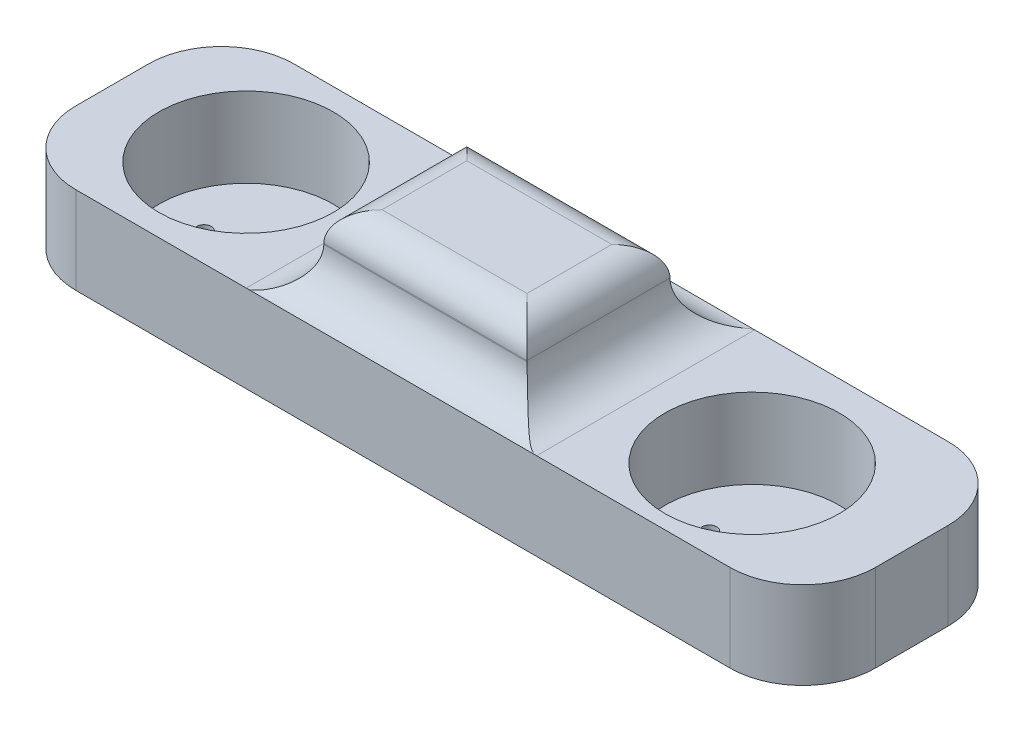
SolidWorks part; units mm, degrees
ref_plane "Front Plane" through (0, 0, 0) normal (0, 0, 1) x (1, 0, 0)
ref_plane "Top Plane" through (0, 0, 0) normal (0, 1, 0) x (1, 0, 0)
ref_plane "Right Plane" through (0, 0, 0) normal (1, 0, 0) x (0, 0, -1)
sketch "Sketch1" plane through (0, 0, 0) normal (0, 1, 0) x (1, 0, 0)
  line L1 (-49.6146, 18.5384) -> (60.3854, 18.5384)
  line L2 (-49.6146, 18.5384) -> (-49.6146, -11.4616)
  line L3 (-49.6146, -11.4616) -> (60.3854, -11.4616)
  line L4 (60.3854, 18.5384) -> (60.3854, -11.4616)
  dimension "D1" = 110
  dimension "D2" = 30
extrude "Boss-Extrude1" add sketch "Sketch1" along normal blind 12
fillet "Fillet1" radius 10 2 edges at (-49.6146, 6, -18.5384) (-49.6146, 6, 11.4616)
fillet "Fillet2" radius 10 2 edges at (60.3854, 6, -18.5384) (60.3854, 6, 11.4616)
sketch "Sketch9" plane through (0, 12, 0) normal (0, 1, 0) x (1, 0, 0)
  line L0 (-39.6146, -11.4616) -> (50.3854, -11.4616) construction
  circle A0 centre (-31.1958, 3.5384) radius 12
  dimension "D1" = 15
extrude "Cut-Extrude5" cut sketch "Sketch9" against normal blind 11
sketch "Sketch13" plane through (70.6968, 12, 1.0722) normal (0, 1, 0) x (1, 0, 0)
  circle A0 centre (-31.1958, 3.5384) radius 12
extrude "Cut-Extrude7" cut sketch "Sketch13" against normal blind 11
sketch "Sketch15" plane through (70.6968, 1, 1.0722) normal (0, 1, 0) x (1, 0, 0)
  circle A0 centre (-31.1477, 3.5384) radius 3.43
  circle A1 centre (-25.2177, 3.5384) radius 1
  circle A2 centre (-37.0777, 3.5384) radius 1
  dimension "D2" = 2.5
  dimension "D3" = 2.5
extrude "Cut-Extrude8" cut sketch "Sketch15" against normal through all
sketch "Sketch16" plane through (70.6968, 1, 1.0722) normal (0, 1, 0) x (1, 0, 0)
  circle A0 centre (-101.6996, 4.5567) radius 3.43
  circle A1 centre (-95.7696, 4.5567) radius 1
  circle A2 centre (-107.6296, 4.5567) radius 1
  dimension "D2" = 2.5
  dimension "D3" = 2.5
extrude "Cut-Extrude9" cut sketch "Sketch16" against normal through all
sketch "Sketch17" plane through (0, 12, 0) normal (0, 1, 0) x (1, 0, 0)
  line L1 (17.7693, -6.7847) -> (-10.1816, -6.7847)
  line L2 (17.7693, -6.7847) -> (17.7693, 12.888)
  line L3 (17.7693, 12.888) -> (-10.1816, 12.888)
  line L4 (-10.1816, -6.7847) -> (-10.1816, 12.888)
  line L5 (17.7693, -6.7847) -> (-10.1816, 12.888) construction
  line L6 (17.7693, 12.888) -> (-10.1816, -6.7847) construction
  point P0 (3.7938, 3.0516)
  point P5 (4.2177, 3.2548)
  point P6 (-10.7084, 13.3948)
  point P7 (3.7938, 3.0516)
extrude "Boss-Extrude2" add sketch "Sketch17" along normal blind 10
fillet "Fillet3" radius 4 4 edges at (17.7693, 22, -3.0516) (3.7938, 22, 6.7847) (-10.1816, 22, -3.0516) (3.7938, 22, -12.888)
fillet "Fillet4" radius 6 4 edges at (17.7693, 12, -3.0516) (3.7938, 12, -12.888) (-10.1816, 12, -3.0516) (3.7938, 12, 6.7847)
